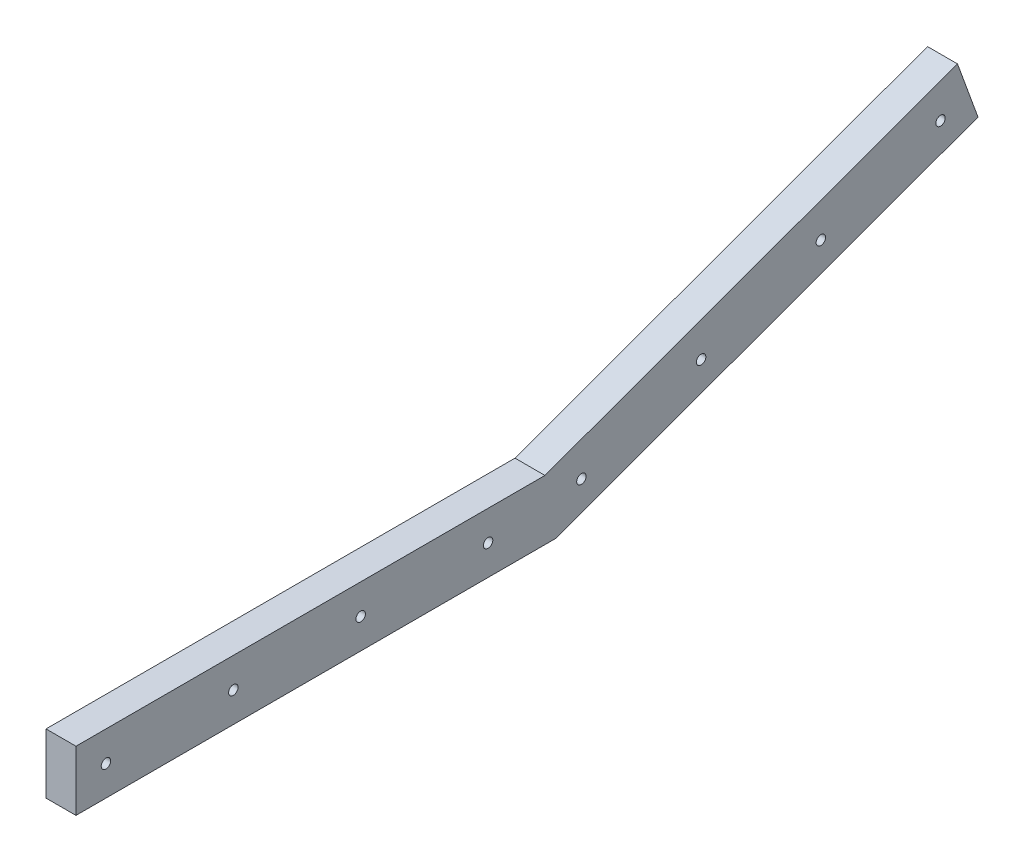
SolidWorks part; units mm, degrees
ref_plane "Front Plane" through (0, 0, 0) normal (0, 0, 1) x (1, 0, 0)
ref_plane "Top Plane" through (0, 0, 0) normal (0, 1, 0) x (1, 0, 0)
ref_plane "Right Plane" through (0, 0, 0) normal (1, 0, 0) x (0, 0, -1)
sketch "Sketch1" plane through (0, 0, 0) normal (1, 0, 0) x (0, 0, -1)
  line L8 (0, 0) -> (-397.4426, 0)
  line L9 (-397.4426, 0) -> (-397.4426, -50.8)
  line L10 (-397.4426, -50.8) -> (8.9574, -50.8)
  line L11 (8.9574, -50.8) -> (366.9803, 79.5097)
  line L12 (0, 0) -> (349.6057, 127.2461)
  line L13 (349.6057, 127.2461) -> (366.9803, 79.5097)
  dimension "D1" = 50.8
  dimension "D2" = 50.8
  dimension "D3" = 406.4
  dimension "D4" = 381
  dimension "D5" = 160
extrude "Boss-Extrude1" add sketch "Sketch1" along normal blind 25.4 contours L8 L9 L10 L11 L13 L12
sketch "Sketch2" plane through (0, 0, 0) normal (-1, 0, 0) x (0, 0, 1)
  line L0 (397.4426, -25.4) -> (-95.6238, -25.4) construction
  line L1 (397.4426, 0) -> (397.4426, -50.8) construction
  line L2 (-358.293, 103.3779) -> (76.3227, -97.1997) construction
  line L3 (-349.6057, 127.2461) -> (-366.9803, 79.5097) construction
  circle A0 centre (372.0426, -25.4) radius 4
  circle A1 centre (-335.2305, 92.7344) radius 4
  dimension "D1" = 8
  dimension "D3" = 8
  dimension "D2" = 25.4
  dimension "D4" = 25.4
extrude "Cut-Extrude1" cut sketch "Sketch2" against normal through all
pattern_linear "LPattern1" count 4 spacing 107.95 along (0, 0, -1) of "Cut-Extrude1"
pattern_linear "LPattern2" count 4 spacing 107.95 along (0, -0.342, 0.9397) of face at (25.4, 92.7344, -331.2305)
equation "\"w\"= 2"
equation "\"l2\"= 15"
equation "\"l1\" = 16"
equation "\"D1@Sketch1\"=\"w\""
equation "\"D2@Sketch1\"=\"2\""
equation "\"D3@Sketch1\"=\"l1\""
equation "\"D4@Sketch1\"=\"l2\""
equation "\"a\"= 180 - 20"
equation "\"D5@Sketch1\"=\"a\""
equation "\"D1@LPattern1\"=(\"l1\"/4.25)"
equation "\"D1@LPattern2\"=\"l2\"/4.25"
